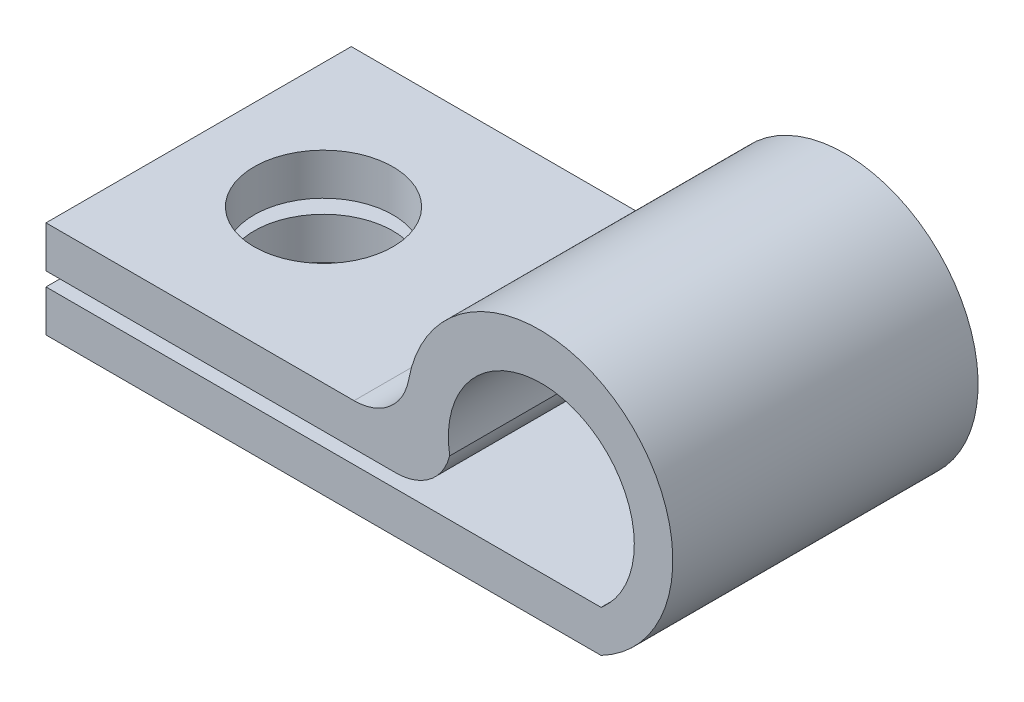
SolidWorks part; units mm, degrees
ref_plane "Front Plane" through (0, 0, 0) normal (0, 0, 1) x (1, 0, 0)
ref_plane "Top Plane" through (0, 0, 0) normal (0, 1, 0) x (1, 0, 0)
ref_plane "Right Plane" through (0, 0, 0) normal (1, 0, 0) x (0, 0, -1)
sketch "Sketch1" plane through (0, 0, 0) normal (0, 0, 1) x (1, 0, 0)
  line L1 (0, 0) -> (-20, 0)
  line L2 (0, 0) -> (0, 1.5)
  line L3 (0, 1.5) -> (-20, 1.5)
  line L4 (-20, 0) -> (-20, 1.5)
  line L5 (-20, 2) -> (-5.4538, 2)
  line L6 (-20, 2) -> (-20, 3.5)
  line L7 (-20, 3.5) -> (-5.4538, 3.5)
  line L8 (-5.4538, 2) -> (-5.4538, 3.5)
  arc A0 (-5.4538, 3.5) -> (0, 1.5) centre (-2.1522, 4.0672) cw
  arc A1 (-6.9538, 3.5) -> (0, 0) centre (-2.2142, 4.2588) cw
  point P10 (-6.9538, 3.5)
  dimension "D6" = 3.35
  dimension "D7" = 1.5
  dimension "D8" = 4.8
  dimension "D1" = 20
  dimension "D2" = 1.5
  dimension "D3" = 1.5
  dimension "D4" = 0.5
  dimension "D5" = 0
  dimension "D9" = 5.4538
extrude "Boss-Extrude1" add sketch "Sketch1" along normal blind 11 contours L5 L8 L7 L6 | A1 L7 A0 L2 | L4 L1 L2 L3 region at (-10, 0.75, 0) region at (0.132, 0.75, 0) region at (-12.7269, 2.75, 0)
ref_plane "Plane1" through (0, 0, 0) normal (0, -1, 0) x (-1, 0, 0)
sketch "Sketch2" plane through (0, 0, 0) normal (0, -1, 0) x (-1, 0, 0)
  line L0 (20, -11) -> (20, 0) construction
  line L1 (0, 0) -> (20, 0) construction
  circle A0 centre (15.5, -5.5) radius 2.5
  point P2 (20, -5.5)
  dimension "D1" = 4.5
  dimension "D2" = 5.5
extrude "Cut-Extrude1" cut sketch "Sketch2" against normal through all
fillet "Fillet1" radius 2 2 edges at (-5.4538, 2, 5.5) (-6.9538, 3.5, 5.5)
